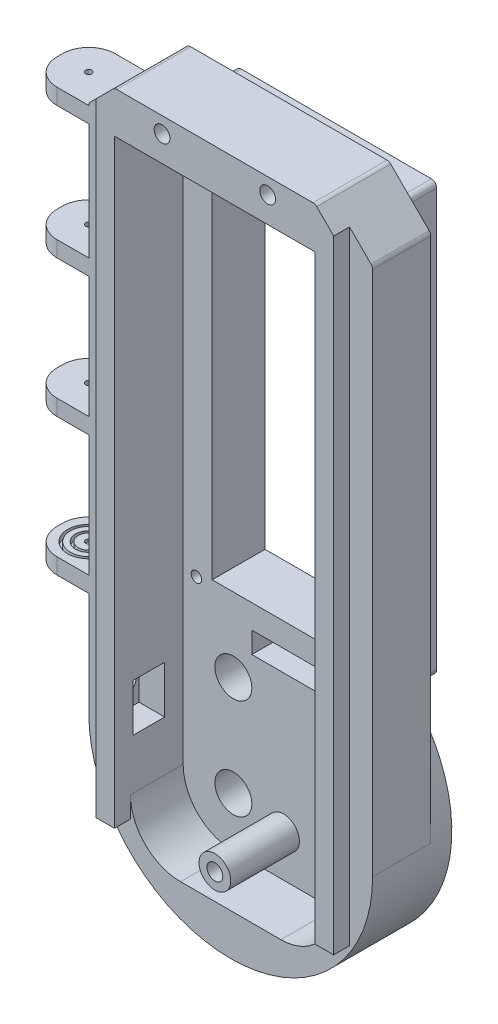
SolidWorks part; units mm, degrees
ref_plane "Alzado" through (0, 0, 0) normal (0, 0, 1) x (1, 0, 0)
ref_plane "Planta" through (0, 0, 0) normal (0, 1, 0) x (1, 0, 0)
ref_plane "Vista lateral" through (0, 0, 0) normal (1, 0, 0) x (0, 0, -1)
sketch "Croquis1" plane through (0, 0, 0) normal (0, 0, 1) x (1, 0, 0)
  line L1 (-19, -40.5) -> (19, -40.5)
  line L2 (-19, -40.5) -> (-19, 40.5)
  line L3 (-19, 40.5) -> (19, 40.5)
  line L4 (19, -40.5) -> (19, 40.5)
  line L5 (-19, -40.5) -> (19, 40.5) construction
  line L6 (-19, 40.5) -> (19, -40.5) construction
  line L7 (-19, -40.5) -> (19, -40.5)
  line L8 (-19, -40.5) -> (-19, -78.5)
  line L9 (-19, -78.5) -> (19, -78.5)
  line L10 (19, -40.5) -> (19, -78.5)
  line L13 (-13.5, 36) -> (13.5, 36)
  line L28 (13.5, 36) -> (13.5, -36)
  line L29 (-13.5, 36) -> (-13.5, -36)
  line L30 (-13.5, -36) -> (13.5, -36)
  circle A0 centre (-9.5, -50) radius 3.5
  circle A1 centre (9.5, -59.5) radius 3.5
  circle A2 centre (-9.5, -69) radius 3.5
  arc A3 (19, -40.5) -> (-19, -40.5) centre (0, -59.5) cw
  point P0 (0, 0)
  point P27 (9.5, -63)
  point P30 (9.5, -54.5)
  point P34 (-13.5, 0)
extrude "Saliente-Extruir1" add sketch "Croquis1" along normal blind 5 contours L1 L4 L3 L2 L30 L29 L13 L28 | L10 L1 L8 L9 A2 A1 A0 | A3 L10 | A3 L9 | A3 L8 region at (-18.1053, 0, 0) region at (0.2752, -59.5, 0) region at (-22.1912, -59.5, 0) region at (22.1912, -59.5, 0) region at (0, -81.6912, 0)
sketch "Croquis2" plane through (0, 0, 0) normal (0, 0, -1) x (-1, 0, 0)
  line L0 (-19, 40.5) -> (19, 40.5)
  line L1 (19, -40.5) -> (-19, -40.5)
  line L2 (-19, -40.5) -> (-19, 40.5)
  line L4 (19, -40.5) -> (19, 40.5)
  line L5 (-13.5, 36) -> (-13.5, -36)
  line L7 (-13.5, -36) -> (13.5, -36)
  line L8 (13.5, -36) -> (13.5, 36)
  line L9 (13.5, 36) -> (-13.5, 36)
extrude "Saliente-Extruir2" add sketch "Croquis2" along normal blind 5
sketch "Croquis3" plane through (0, 0, 5) normal (0, 0, 1) x (1, 0, 0)
  line L0 (26.8701, -59.5) -> (26.8701, 40.5)
  line L1 (19, -59.5) -> (19, 40.5)
  line L2 (19, 40.5) -> (-19, 40.5)
  line L3 (-19, 40.5) -> (-19, -59.5)
  line L4 (26.8701, 40.5) -> (19, 48.3701)
  line L5 (19, 48.3701) -> (-19, 48.3701)
  line L6 (-19, 48.3701) -> (-26.8701, 40.5)
  line L7 (-26.8701, 40.5) -> (-26.8701, -59.5)
  arc A2 (-19, -59.5) -> (19, -59.5) centre (0, -59.5) ccw
  arc A3 (-26.8701, -59.5) -> (26.8701, -59.5) centre (0, -59.5) ccw
extrude "Saliente-Extruir9" add sketch "Croquis3" against normal blind 1
sketch "Croquis4" plane through (0, 0, 4) normal (0, 0, -1) x (-1, 0, 0)
  line L0 (-19, 40.5) -> (-19, -40.5)
  line L1 (-19, 40.5) -> (19, 40.5)
  line L2 (19, 40.5) -> (19, -40.5)
  line L3 (14, -77) -> (-14, -77)
  line L4 (-19, -72) -> (-19, -41.338)
  line L5 (19, -72) -> (19, -40.5)
  line L6 (-26.8701, 40.5) -> (-19, 48.3701)
  line L7 (-19, 48.3701) -> (19, 48.3701)
  line L8 (19, 48.3701) -> (26.8701, 40.5)
  line L9 (26.8701, 40.5) -> (26.8701, -59.5)
  line L10 (-26.8701, 40.5) -> (-26.8701, -59.5)
  arc A0 (-19, -40.5) -> (-26.8701, -59.5) centre (0, -59.5) ccw construction
  arc A1 (-14, -77) -> (-19, -72) centre (-14, -72) cw
  arc A2 (14, -77) -> (19, -72) centre (14, -72) ccw
  arc A3 (-19, -40.5) -> (19, -40.5) centre (0, -59.5) ccw construction
  arc A4 (-26.8701, -59.5) -> (26.8701, -59.5) centre (0, -59.5) ccw
  arc M1 (19, -40.5) -> (26.8701, -59.5) centre (0, -59.5) cw
  line M2 (26.8701, -59.5) -> (26.8701, 40.5)
  line M3 (26.8701, 40.5) -> (19, 48.3701)
  line M4 (19, 48.3701) -> (-19, 48.3701)
  line M5 (-19, 48.3701) -> (-26.8701, 40.5)
  line M6 (-26.8701, 40.5) -> (-26.8701, -59.5)
  arc M7 (-26.8701, -59.5) -> (-19, -40.5) centre (0, -59.5) cw
  line M8 (-19, -40.5) -> (-19, 40.5)
  line M9 (-19, 40.5) -> (19, 40.5)
  line M10 (19, 40.5) -> (19, -40.5)
  dimension "D1" = 5
extrude "Saliente-Extruir10" add sketch "Croquis4" against normal blind 11 contours M10 M1 M2 M3 M4 M5 M6 M7 M8 M9 region at (20.2052, 0, 4)
sketch "Croquis5" plane through (0, 0, 5) normal (0, 0, 1) x (1, 0, 0)
  line L0 (-19, -59.5) -> (-19, -69)
  line L1 (19, -69) -> (19, -59.5)
  line L2 (9.5, -78.5) -> (-9.5, -78.5)
  line L3 (19, -59.5) -> (19, -40.5)
  line L4 (-19, -59.5) -> (-19, -40.5)
  arc A0 (-19, -40.5) -> (19, -40.5) centre (0, -59.5) ccw
  arc A1 (-9.5, -78.5) -> (-19, -69) centre (-9.5, -69) cw
  arc A2 (9.5, -78.5) -> (19, -69) centre (9.5, -69) ccw
extrude "Saliente-Extruir11" add sketch "Croquis5" along normal blind 10
fillet "Redondeo1" radius 1 4 edges at (-19, -40.5, -2.5) (-19, 40.5, -0.5) (19, 40.5, -0.5) (19, -40.5, -2.5)
fillet "Redondeo2" radius 1 5 edges at (-18.7071, 40.2071, 4) (18.7071, 40.2071, 4) (-19, -0.5, 4) (0, 40.5, 4) (19, -0.5, 4)
fillet "Redondeo3" radius 1 4 edges at (-26.8701, 40.5, 9.5) (-19, 48.3701, 9.5) (26.8701, 40.5, 9.5) (19, 48.3701, 9.5)
sketch "Croquis6" plane through (-26.8701, 0, 0) normal (-1, 0, 0) x (0, 0, 1)
  line L2 (8.5, -50.5) -> (14.5, -50.5)
  line L3 (14.5, -50.5) -> (14.5, -59.5)
  line L4 (14.5, -59.5) -> (8.5, -59.5)
  line L5 (8.5, -50.5) -> (8.5, -59.5)
extrude "Cortar-Extruir1" cut sketch "Croquis6" against normal blind 8
sketch "Croquis7" plane through (-26.8701, 0, 0) normal (-1, 0, 0) x (0, 0, 1)
  line L0 (8.5, -50.5) -> (14.5, -50.5)
  line L1 (14.5, -50.5) -> (14.5, -59.5)
  line L2 (14.5, -59.5) -> (8.5, -59.5)
  line L3 (8.5, -59.5) -> (8.5, -50.5)
  circle A0 centre (11.5, -55) radius 2.5
extrude "Saliente-Extruir12" add sketch "Croquis7" against normal blind 3
sketch "Croquis8" plane through (-26.8701, 0, 0) normal (-1, 0, 0) x (0, 0, 1)
  line L0 (4, 40.0858) -> (4, 37.0858)
  line L1 (4, 39.5) -> (4, -41.5556) construction
  line L2 (4, 37.0858) -> (15, 37.0858)
  line L3 (15, -59.5) -> (15, 40.0858) construction
  line L4 (15, 37.0858) -> (15, 40.0858)
  line L5 (15, 40.0858) -> (4, 40.0858)
  line L6 (9.5, 37.0858) -> (9.5, 15.0858)
  line L7 (9.5, 15.0858) -> (15, 15.0858)
  line L8 (9.5, 15.0858) -> (4, 15.0858)
  line L9 (4, 15.0858) -> (4, 12.0858)
  line L10 (4, 40.0858) -> (4, -59.5) construction
  line L11 (4, 12.0858) -> (15, 12.0858)
  line L12 (15, 12.0858) -> (15, 15.0858)
  line L13 (9.5, 12.0858) -> (9.5, -10.9142)
  line L14 (9.5, -10.9142) -> (15, -10.9142)
  line L15 (15, -10.9142) -> (15, -13.9142)
  line L16 (15, -13.9142) -> (4, -13.9142)
  line L17 (4, -13.9142) -> (4, -10.9142)
  line L18 (4, -10.9142) -> (9.5, -10.9142)
  line L19 (9.5, -13.9142) -> (9.5, -36.9142)
  line L20 (9.5, -36.9142) -> (15, -36.9142)
  line L21 (15, -36.9142) -> (15, -39.9142)
  line L22 (15, -39.9142) -> (4, -39.9142)
  line L23 (4, -39.9142) -> (4, -36.9142)
  line L24 (4, -36.9142) -> (9.5, -36.9142)
  line M2 (15, -59.5) -> (15, 40.0858)
  line M3 (15, 40.0858) -> (4, 40.0858)
  line M4 (4, 40.0858) -> (4, -59.5)
extrude "Saliente-Extruir13" add sketch "Croquis8" along normal blind 11 contours L2 M4 M2 M3 | L11 L7 L8 M4 M2 | L18 L16 L14 M4 M2 | L24 L22 L20 M4 M2 region at (-26.8701, 38.5858, 9.5) region at (-26.8701, 13.5858, 9.5) region at (-26.8701, -12.4142, 9.5) region at (-26.8701, -38.4142, 9.5)
fillet "Redondeo4" radius 5 8 edges at (-37.8701, -38.4142, 4) (-37.8701, -38.4142, 15) (-37.8701, -12.4142, 4) (-37.8701, -12.4142, 15) (-37.8701, 13.5858, 4) (-37.8701, 13.5858, 15) (-37.8701, 38.5858, 4) (-37.8701, 38.5858, 15)
sketch "Croquis9" plane through (0, 40.0858, 0) normal (0, 1, 0) x (1, 0, 0)
  circle A0 centre (-32.3701, -9.5) radius 0.6
extrude "Cortar-Extruir2" cut sketch "Croquis9" against normal blind 80
sketch "Croquis10" plane through (0, -39.9142, 0) normal (0, -1, 0) x (1, 0, 0)
  circle A0 centre (-32.3701, 9.5) radius 0.6
extrude "Saliente-Extruir14" add sketch "Croquis10" against normal blind 2.5
sketch "Croquis11" plane through (0, -36.9142, 0) normal (0, 1, 0) x (1, 0, 0)
  circle A0 centre (-32.3701, -9.5) radius 2
  circle A1 centre (-32.3701, -9.5) radius 2.5
  circle A2 centre (-32.3701, -9.5) radius 3.5
  circle A3 centre (-32.3701, -9.5) radius 4
extrude "Cortar-Extruir3" cut sketch "Croquis11" against normal blind 1 contours A3 A2 | A1 A0 region at (-34.7993, -36.9142, 9.5) region at (-36.2569, -36.9142, 9.5)
sketch "Croquis13" plane through (0, 0, 15) normal (0, 0, 1) x (1, 0, 0)
  line L0 (19, 40.5) -> (22.5, 40.5)
  line L1 (19, -69) -> (22.5, -69)
  line L2 (22.5, -69) -> (22.5, 40.5)
  line L3 (19, -69) -> (19, 40.5)
  line L5 (22.5, 40.5) -> (22.5, 44.8701)
  line L6 (-19, -69) -> (-19, 40.5)
  line L7 (-22.5, -69) -> (-22.5, 40.5)
  line L8 (-19, -69) -> (-22.5, -69)
  line L9 (-19, 40.5) -> (-22.5, 40.5)
  line L10 (-19, -69) -> (-19, -65.5)
  line L12 (19, -65.5) -> (19, -69)
  line L13 (-22.5, 40.5) -> (-22.5, 44.8701)
  line L14 (-26.5772, 40.7929) -> (-19.2929, 48.0772) construction
  line L15 (-22.5, 44.8701) -> (-19.2929, 48.0772)
  line L16 (-18.5858, 48.3701) -> (18.5858, 48.3701)
  line L19 (22.5, 44.8701) -> (19.2929, 48.0772)
  arc A0 (-19.2929, 48.0772) -> (-18.5858, 48.3701) centre (-18.5858, 47.3701) cw
  arc A1 (19.2929, 48.0772) -> (18.5858, 48.3701) centre (18.5858, 47.3701) ccw
  line M1 (19, 40.5) -> (19, -69)
  line M5 (-19, -69) -> (-19, 40.5)
  line M6 (-19, 40.5) -> (19, 40.5)
  line M14 (26.5772, 40.7929) -> (19.2929, 48.0772)
  arc M15 (19.2929, 48.0772) -> (18.5858, 48.3701) centre (18.5858, 47.3701) ccw
  line M16 (18.5858, 48.3701) -> (-18.5858, 48.3701)
  arc M17 (-18.5858, 48.3701) -> (-19.2929, 48.0772) centre (-18.5858, 47.3701) ccw
  line M18 (-19.2929, 48.0772) -> (-26.5772, 40.7929)
extrude "Saliente-Extruir15" add sketch "Croquis13" along normal blind 3 contours L6 L9 L7 L8 M5 | L1 L2 L0 L3 M1 | L13 L9 L0 L5 M6 M14 M15 M16 M17 M18 region at (0, 44.3353, 15) region at (20.75, -14.25, 15) region at (-20.75, -14.25, 15)
sketch "Croquis14" plane through (0, 0, 4) normal (0, 0, -1) x (-1, 0, 0)
  circle A0 centre (10, 45.3701) radius 1.5
  circle A1 centre (-10, 45.3701) radius 1.5
extrude "Cortar-Extruir4" cut sketch "Croquis14" against normal blind 14
sketch "Croquis16" plane through (0, -69, 0) normal (0, -1, 0) x (-1, 0, 0)
  line L1 (22.5, -15) -> (19, -15)
  line L2 (22.5, -15) -> (22.5, -18)
  line L3 (22.5, -18) -> (19, -18)
  line L4 (-19, -15) -> (-22.5, -15)
  line L5 (-19, -15) -> (-19, -18)
  line L6 (-19, -18) -> (-22.5, -18)
  line L7 (-22.5, -15) -> (-22.5, -18)
  line L8 (19, -15) -> (19, -18)
extrude "Saliente-Extruir16" add sketch "Croquis16" along normal blind 4
sketch "Croquis25" plane through (0, 0, 18) normal (0, 0, 1) x (1, 0, 0)
  line L0 (-10, 45.3701) -> (10, 45.3701)
  line L1 (0, 45.3701) -> (0, -70.6299)
  circle A0 centre (0, -70.6299) radius 3
  circle A1 centre (0, -70.6299) radius 1.5
extrude "Saliente-Extruir21" add sketch "Croquis25" against normal blind 18 contours A1 A0 region at (2.0613, -68.5686, 18)
sketch "Croquis26" plane through (0, 0, 18) normal (0, 0, 1) x (1, 0, 0)
  circle A0 centre (0, -70.6299) radius 1.5
extrude "Cortar-Extruir7" cut sketch "Croquis26" against normal blind 18
sketch "Croquis28" plane through (0, 0, 5) normal (0, 0, 1) x (1, 0, 0)
  circle A0 centre (-16.5, 38) radius 1
  circle A1 centre (14.5, 38) radius 1
  circle A2 centre (14.5, -37) radius 1
  circle A3 centre (-16.5, -37) radius 1
extrude "Cortar-Extruir8" cut sketch "Croquis28" against normal blind 4
sketch "Croquis29" plane through (0, 0, 5) normal (0, 0, 1) x (1, 0, 0)
  line L2 (-6, -40.5) -> (10, -40.5)
  line L3 (10, -40.5) -> (10, -44.5)
  line L4 (10, -44.5) -> (-6, -44.5)
  line L6 (-6, -40.5) -> (-6, -44.5)
extrude "Cortar-Extruir9" cut sketch "Croquis29" against normal up to surface (5 mm away) up to face at (1.5, -70.6299, 0)
